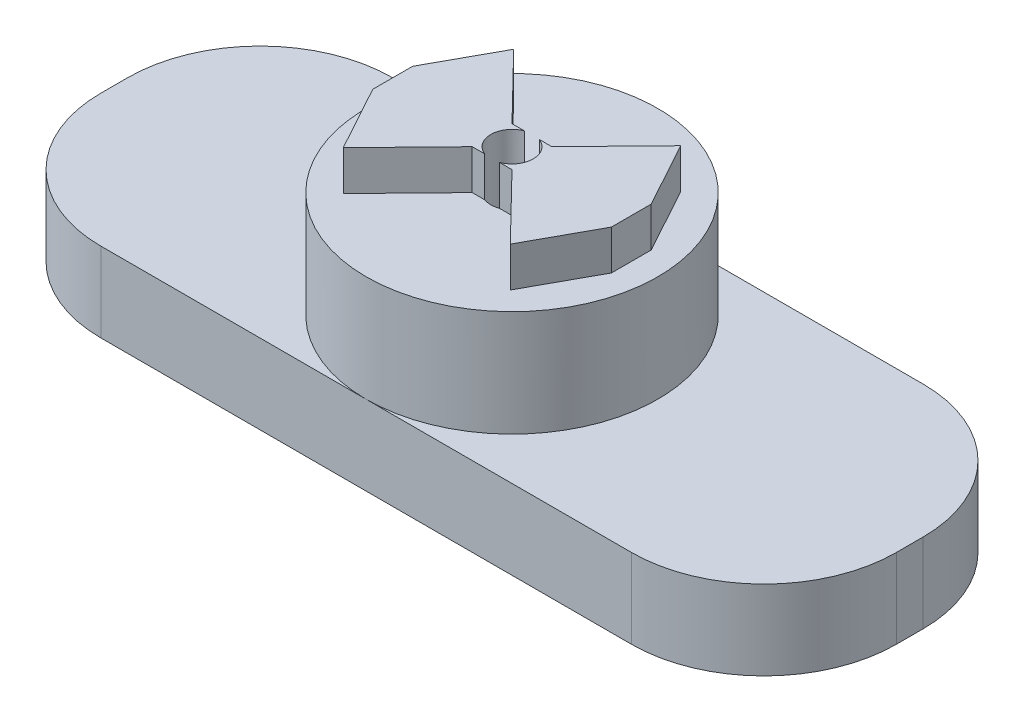
SolidWorks part; units mm, degrees
ref_plane "Płaszczyzna przednia" through (0, 0, 0) normal (0, 0, 1) x (1, 0, 0)
ref_plane "Płaszczyzna górna" through (0, 0, 0) normal (0, 1, 0) x (1, 0, 0)
ref_plane "Płaszczyzna prawa" through (0, 0, 0) normal (1, 0, 0) x (0, 0, -1)
sketch "Sketch1" plane through (0, 0, 0) normal (0, 1, 0) x (1, 0, 0)
  line L5 (-20.01, -11) -> (20.01, -11)
  line L6 (-30, -1.01) -> (-30, 1.01)
  line L7 (-20.01, 11) -> (20.01, 11)
  line L8 (30, -1.01) -> (30, 1.01)
  line L9 (-30, -11) -> (30, 11) construction
  line L10 (-30, 11) -> (30, -11) construction
  arc A0 (-20.01, -11) -> (-30, -1.01) centre (-20.01, -1.01) cw
  arc A1 (20.01, -11) -> (30, -1.01) centre (20.01, -1.01) ccw
  arc A2 (20.01, 11) -> (30, 1.01) centre (20.01, 1.01) cw
  arc A3 (-30, 1.01) -> (-20.01, 11) centre (-20.01, 1.01) cw
  point P0 (0, 0)
  point P1 (0, 0)
  dimension "D3" = 9.99
  dimension "D1" = 60
  dimension "D2" = 22
extrude "Boss-Extrude1" add sketch "Sketch1" along normal blind 6
sketch "Sketch2" plane through (0, 6, 0) normal (0, 1, 0) x (1, 0, 0)
  line L0 (0, 0) -> (-3, 0) construction
  line L1 (0, 0) -> (3, 0) construction
  circle A3 centre (0, 0) radius 11
extrude "Boss-Extrude2" add sketch "Sketch2" along normal blind 8
sketch "Sketch12" plane through (0, 0, 0) normal (0, -1, 0) x (1, 0, 0)
  circle A0 centre (0, 0) radius 6
extrude "Cut-Extrude2" cut sketch "Sketch12" against normal blind 4
sketch "Sketch18" plane through (0, 4, 0) normal (0, -1, 0) x (-1, 0, 0)
  point P0 (0, 0)
sketch "Sketch19" plane through (0, 14, 0) normal (0, 1, 0) x (1, 0, 0)
  line L26 (-6.3004, 6.4269) -> (-9, 1.5)
  line L27 (-1.5, -1.5) -> (1.5, -1.5) construction
  line L28 (-1.5, -1.5) -> (-1.5, 1.5) construction
  line L29 (-1.5, 1.5) -> (1.5, 1.5) construction
  line L30 (1.5, -1.5) -> (1.5, 1.5) construction
  line L31 (-1.5, -1.5) -> (1.5, 1.5) construction
  line L32 (-1.5, 1.5) -> (1.5, -1.5) construction
  line L33 (-6.3004, -6.4269) -> (6.3004, -6.4269) construction
  line L34 (-6.3004, -6.4269) -> (-6.3004, 6.4269) construction
  line L35 (-6.3004, 6.4269) -> (6.3004, 6.4269) construction
  line L36 (6.3004, -6.4269) -> (6.3004, 6.4269) construction
  line L37 (-6.3004, -6.4269) -> (6.3004, 6.4269) construction
  line L38 (-6.3004, 6.4269) -> (6.3004, -6.4269) construction
  line L39 (-9, -1.5) -> (9, -1.5) construction
  line L40 (-9, -1.5) -> (-9, 1.5) construction
  line L41 (-9, 1.5) -> (9, 1.5) construction
  line L42 (9, -1.5) -> (9, 1.5) construction
  line L43 (-9, -1.5) -> (9, 1.5) construction
  line L44 (-9, 1.5) -> (9, -1.5) construction
  line L45 (-9, 1.5) -> (-9, -1.5)
  line L46 (-9, -1.5) -> (-6.3004, -6.4269)
  line L47 (-6.3004, -6.4269) -> (-1.5, -1.5)
  line L48 (-1.5, -1.5) -> (1.5, -1.5)
  line L49 (1.5, -1.5) -> (6.3004, -6.4269)
  line L50 (6.3004, -6.4269) -> (9, -1.5)
  line L51 (9, -1.5) -> (9, 1.5)
  line L52 (9, 1.5) -> (6.3004, 6.4269)
  line L53 (6.3004, 6.4269) -> (1.5, 1.5)
  line L54 (1.5, 1.5) -> (-1.5, 1.5)
  line L55 (-1.5, 1.5) -> (-6.3004, 6.4269)
  point P16 (0, 0)
  point P22 (0, 0)
  point P27 (0, 0)
  dimension "D1" = 12.6008
  dimension "D2" = 12.8538
  dimension "D4" = 3
  dimension "D5" = 3
  dimension "D6" = 18
  dimension "D7" = 18
extrude "Boss-Extrude3" add sketch "Sketch19" along normal blind 3
hole_wizard "CSK for M3 Countersunk Flat Head Screw3" positions "Sketch18" profile "Sketch17" countersink size "M3" standard "ISO" end condition through all
sketch "Sketch17" plane through (0, 4, 0) normal (1, 0, 0) x (0, 0, -1)
  line L0 (0, 0) -> (0, 13)
  line L1 (0, 13) -> (1.6, 13)
  line L2 (1.6, 13) -> (1.6, 1.55)
  line L3 (1.6, 1.55) -> (3.15, 0)
  line L5 (3.15, 0) -> (0, 0)
  line L6 (-1.6, 1.55) -> (-3.15, 0) construction
  line L11 (0, -6.35) -> (0, 107.95) construction
  dimension "Thru Hole Dia." = 3.2
  dimension "Thru Hole Depth" = 13
  dimension "Near C'Sink Dia." = 6.3
  dimension "Near C'Sink Angle" = 90
